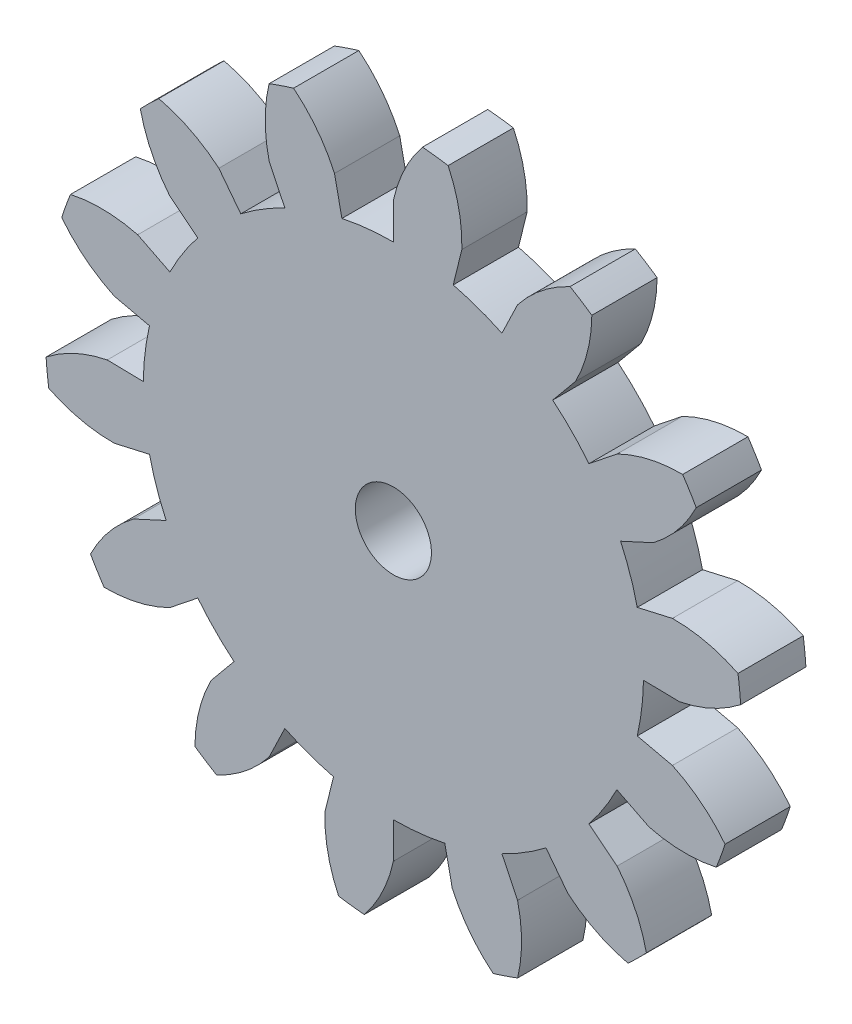
SolidWorks part; units mm, degrees
ref_plane "Plan de face" through (0, 0, 0) normal (0, 0, 1) x (1, 0, 0)
ref_plane "Plan de dessus" through (0, 0, 0) normal (0, 1, 0) x (1, 0, 0)
ref_plane "Plan de droite" through (0, 0, 0) normal (1, 0, 0) x (0, 0, -1)
sketch "Esquisse1" plane through (0, 0, 0) normal (0, 0, 1) x (1, 0, 0)
  circle A0 centre (0, 0) radius 14
  circle A1 centre (0, 0) radius 16
  circle A2 centre (0, 0) radius 11.5
  circle A3 centre (0, 0) radius 12
  circle A4 centre (0, 0) radius 13.1557
  dimension "Pitch Circle" = 28
  dimension "Addendum Circle" = 32
  dimension "Root Circle" = 23
  dimension "Clearence Circle" = 24
  dimension "Base Circle" = 26.3114
sketch "Involute" plane through (0, 0, 0) normal (0, 0, 1) x (1, 0, 0)
  line L0 (0, 0) -> (0, 13.1557)
  line L1 (0, 0) -> (6.5778, 11.3932) construction
  line L2 (0, 0) -> (11.3932, 6.5778) construction
  line L3 (0, 0) -> (13.1557, 0) construction
  line L4 (13.1557, 0) -> (13.1557, 20.6649) construction
  line L5 (11.3932, 6.5778) -> (4.5049, 18.5087) construction
  line L6 (6.5778, 11.3932) -> (0.6124, 14.8373) construction
  line L7 (0, 0) -> (3.1153, 13.649) construction
  line L8 (6.0744, 12.6136) -> (0, 0)
  line L9 (1.6873, 13.898) -> (0, 0) construction
  circle A0 centre (0, 0) radius 13.1557 construction
  circle A1 centre (0, 0) radius 14 construction
  arc A2 (3.1153, 13.649) -> (0.2412, 13.9979) centre (0, 0) ccw
  spline S0 degree 3 poles (0, 13.1557) (1.1572, 18.5432) (8.7162, 20.6719) (13.1557, 20.6649) knots 0 0 0 0 1 1 1 1
  spline S1 degree 3 poles (3.1479, 12.7735) (3.3134, 18.2814) (-3.5166, 22.1571) (-7.8288, 23.2125) knots 0 0 0 0 1 1 1 1
  dimension "Involute Control" = 90
  dimension "Base Circle Quarter Circumference" = 20.6649
  dimension "D1" = 13.7766
  dimension "D2" = 6.8883
  dimension "Circular Pitch" = 25.714
  dimension "Involute Array" = 4
sketch "Esquisse4" plane through (0, 0, 0) normal (0, 0, 1) x (1, 0, 0)
  line L0 (0, 0) -> (0, 13.1557) construction
  line L1 (0, 13.1557) -> (0, 11.5)
  line L2 (3.1479, 12.7735) -> (2.7518, 11.1659)
  arc A0 (1.3368, 15.9441) -> (2.5172, 15.8007) centre (0, 0) cw
  circle A1 centre (0, 0) radius 16 construction
  arc A2 (0, 11.5) -> (2.7518, 11.1659) centre (0, 0) cw
  circle A3 centre (0, 0) radius 11.5 construction
  arc A4 (0, 13.1557) -> (1.3368, 15.9441) centre (6.5215, 11.7438) cw
  arc A5 (2.5172, 15.8007) -> (3.1479, 12.7735) centre (-3.522, 12.9632) cw
  spline S0 degree 3 poles (0, 13.1557) (1.1572, 18.5432) (8.7162, 20.6719) (13.1557, 20.6649) knots 0 0 0 0 1 1 1 1 construction
  spline S1 degree 3 poles (3.1479, 12.7735) (3.3134, 18.2814) (-3.5166, 22.1571) (-7.8288, 23.2125) knots 0 0 0 0 1 1 1 1 construction
extrude "Boss.-Extru.1" add sketch "Esquisse4" along normal blind 3
ref_axis "Axe1" through (0, 0, 0) along (0, 0, 1)
pattern_circular "Répétition circulaire2" count 14 over 360 about axis through (0, 0, 0) along (0, 0, 1) of bodies 101
sketch "Esquisse5" plane through (0, 0, 0) normal (0, 0, 1) x (1, 0, 0)
  circle A0 centre (0, 0) radius 11.5 construction
  circle A1 centre (0, 0) radius 11.5
extrude "Boss.-Extru.2" add sketch "Esquisse5" along normal up to surface (3 mm away) up to face at (-9.4798, 9.6446, 3)
sketch "Esquisse6" plane through (0, 0, 0) normal (0, 0, -1) x (-1, 0, 0)
  line L0 (0, 0) -> (0, 1.75) construction
  circle A0 centre (0, 0) radius 1.75
  dimension "D4" = 3.5
extrude "Enlèv. mat.-Extru.1" cut sketch "Esquisse6" against normal through all
equation "\"Module\"= 2"
equation "\"Nb de dents\"= 14"
equation "\"Pressure Angle\"= 20"
equation "\"Pitch Circle@Esquisse1\"= \"Module\" * \"Nb de dents\""
equation "\"Addendum Circle@Esquisse1\"= \"Pitch Circle@Esquisse1\" + ( \"Module\" * 2 )"
equation "\"Clearence Circle@Esquisse1\"= \"Pitch Circle@Esquisse1\" - ( \"Module\" * 2 )"
equation "\"Root Circle@Esquisse1\"= \"Pitch Circle@Esquisse1\" - ( ( \"Module\" * 1.25 ) * 2 )"
equation "\"Base Circle@Esquisse1\"= \"Pitch Circle@Esquisse1\" * cos ( \"Pressure Angle\" )"
equation "\"Base Circle Quarter Circumference@Involute\" = \"Base Circle@Esquisse1\" * pI / 4"
equation "\"D1@Involute\"=\"Base Circle Quarter Circumference@Involute\"/3*2"
equation "\"D2@Involute\"=\"Base Circle Quarter Circumference@Involute\"/3"
equation "\"Circular Pitch@Involute\"=360/\"Nb de dents\""
equation "\"D1@Répétition circulaire2\"= \"Nb de dents\""
